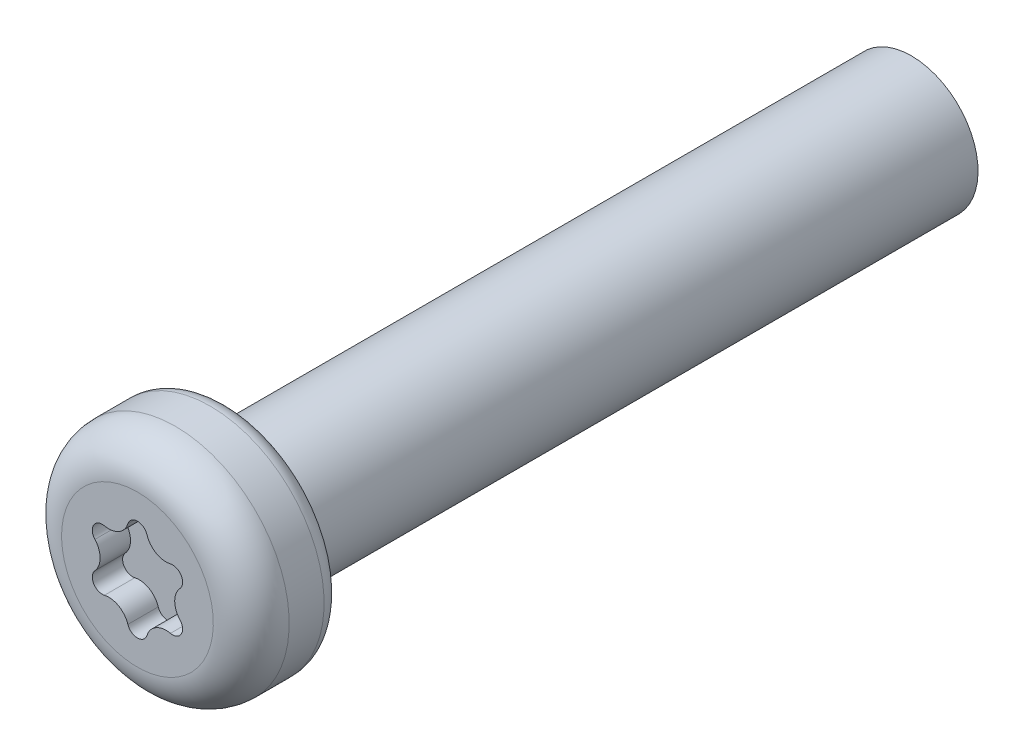
SolidWorks part; units mm, degrees
material "AISI 304 Stainless Steel"
ref_plane "Front" through (0, 0, 0) normal (0, 0, 1) x (1, 0, 0)
ref_plane "Top" through (0, 0, 0) normal (0, 1, 0) x (1, 0, 0)
ref_plane "Right" through (0, 0, 0) normal (1, 0, 0) x (0, 0, -1)
sketch "Sketch17" plane through (0, 0, 0) normal (1, 0, 0) x (0, 0, -1)
  line L0 (12, 1.17) -> (12, -1.17) construction
  line L1 (0, 0) -> (12, 0)
  line L2 (0, 0) -> (0, 1.17)
  line L3 (0, 1.17) -> (12, 1.17)
  line L4 (12, 0) -> (12, 1.17)
  line L5 (11.298, 0.9224) -> (10.596, 1.0462) construction
  line L6 (10.596, 1.0462) -> (10.596, 1.17) construction
  line L7 (11.298, 0.9224) -> (12, 0.7987) construction
  line L8 (10.596, 1.0462) -> (9.894, 1.17) construction
  dimension "D1" = 10
  dimension "Body Length" = 12
  dimension "Dia" = 2.34
  dimension "D2" = 1.404
revolve "Revolve1" add sketch "Sketch17" angle 360 about L11
ref_plane "Plane1" through (0, 0, -9.894) normal (0, 0, 1) x (1, 0, 0)
sketch "Sketch1" plane through (0, 0, 0) normal (0, 0, 1) x (1, 0, 0)
  circle A0 centre (0, 0) radius 2
  dimension "Head Dia" = 4
extrude "Extrude3" add sketch "Sketch1" along normal blind 1.6
sketch "Sketch11" plane through (0, 0, 0) normal (1, 0, 0) x (0, 0, -1)
  line L2 (-1.6, 2) -> (-1.6, -2) construction
  line L4 (0, 2) -> (-1.6, 2) construction
  line L5 (-0.9333, 2) -> (-0.32, 2)
  line L6 (0, -2) -> (0, 2) construction
  line L7 (-1.6, 2) -> (-1.6, 1.3333) construction
  line L8 (-1.6, 0.6667) -> (-1.6, 0) construction
  line L9 (-1.6, 1.3333) -> (-1.6, 0.6667) construction
  line L10 (-1.6, 1.3333) -> (-1.854, 1.3333)
  line L11 (0, 0) -> (-1.6, 0) construction
  line L12 (-1.854, 1.3333) -> (-1.854, 2.254)
  line L13 (-1.854, 2.254) -> (0.254, 2.254)
  line L14 (0.254, 2.254) -> (0.254, 1.68)
  line L15 (0.254, 1.68) -> (0, 1.68)
  arc A0 (-1.6, 1.3333) -> (-0.9333, 2) centre (-0.9333, 1.3333) cw
  arc A1 (-0.32, 2) -> (0, 1.68) centre (-0.32, 1.68) cw
  dimension "D1" = 0.32
  dimension "D2" = 0.254
  dimension "D3" = 0.254
revolve "Cut-Revolve3" cut sketch "Sketch11" angle 360 about L11
sketch "Sketch12" plane through (0, 0, 1.6) normal (0, 0, 1) x (1, 0, 0)
  line L0 (0, 0) -> (0, 0.8889) construction
  line L1 (0, 0) -> (0.3275, 0.5672) construction
  line L2 (0, 0) -> (-0.3275, 0.5672) construction
  line L3 (-0.3275, 0.5672) -> (0, 0)
  line L4 (0, 0) -> (0.3275, 0.5672)
  arc A0 (-0.3275, 0.5672) -> (-0.1678, 0.7659) centre (-0.5035, 0.872) ccw
  arc A1 (-0.1678, 0.7659) -> (0.1678, 0.7659) centre (0, 0.7129) cw
  arc A2 (0.1678, 0.7659) -> (0.3275, 0.5672) centre (0.5035, 0.872) ccw
  circle A5 centre (0, 0) radius 0.8889 construction
  dimension "D1" = 60
  dimension "M" = 1.7778
  dimension "D2" = 0.176
  dimension "D3" = 0.352
extrude "Cut-Extrude1" cut sketch "Sketch12" against normal blind 0.5333
ref_axis "Axis1" through (0, 0, 1.6) along (0, 0, -1)
pattern_circular "CirPattern1" count 6 over 360 of "Cut-Extrude1"
equation "\"D1@Cut-Extrude1\"=\"Head Ht@Extrude3\"/3"
equation "\"D1@Sketch11\" = \"Head Ht@Extrude3\"/5"
equation "\"M@Sketch12\" = \"Head Dia@Sketch1\"/2.25"
equation "\"D2@Sketch12\" = \"Head Dia@Sketch1\" * .044"
equation "\"D3@Sketch12\" = \"D2@Sketch12\" * 2"
equation "\"D2@Sketch17\" = \"Dia@Sketch17\" * .6"
